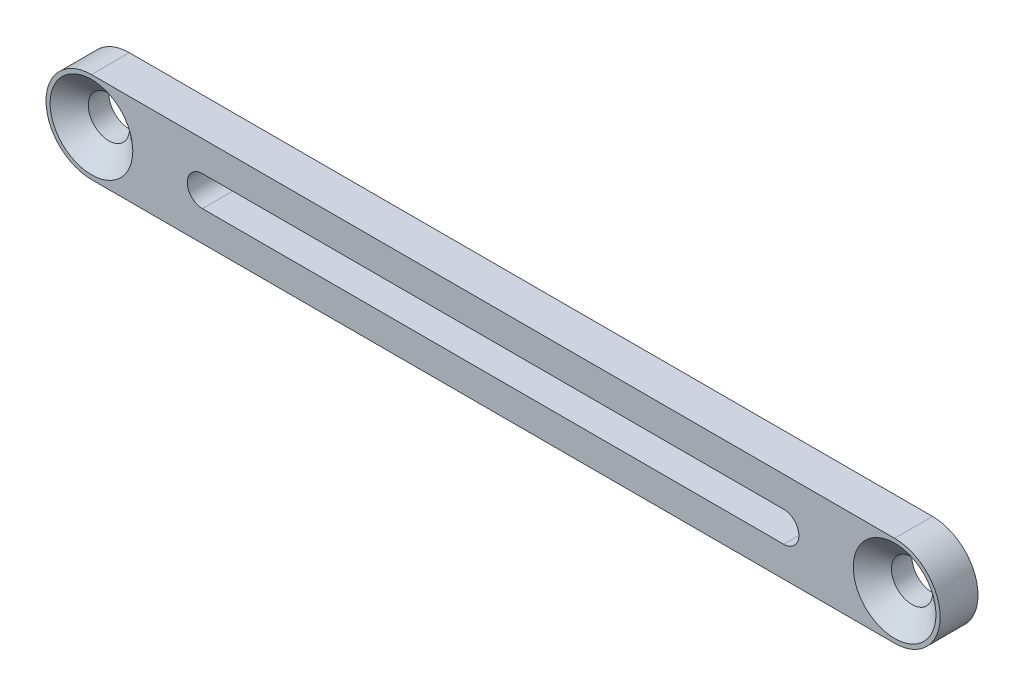
SolidWorks part; units mm, degrees
material "ABS"
ref_plane "Front Plane" through (0, 0, 0) normal (0, 0, 1) x (1, 0, 0)
ref_plane "Top Plane" through (0, 0, 0) normal (0, 1, 0) x (1, 0, 0)
ref_plane "Right Plane" through (0, 0, 0) normal (1, 0, 0) x (0, 0, -1)
sketch "Sketch1" plane through (0, 0, 0) normal (0, 0, 1) x (1, 0, 0)
  line L0 (5.4696, 20.4127) -> (72.7692, 20.4127) construction
  line L1 (5.4696, 16.6027) -> (72.7692, 16.6027)
  line L2 (5.4696, 24.2227) -> (72.7692, 24.2227)
  arc A0 (5.4696, 16.6027) -> (5.4696, 24.2227) centre (5.4696, 20.4127) cw
  arc A1 (72.7692, 16.6027) -> (72.7692, 24.2227) centre (72.7692, 20.4127) ccw
  dimension "D1" = 3.81
  dimension "D2" = 3.81
extrude "Boss-Extrude1" add sketch "Sketch1" along normal blind 3.175
hole_wizard "CSK for #4 Flat Head Machine Screw (100)1" positions "Sketch3" profile "Sketch2" countersink size "#4" standard "ANSI Inch" end condition through all
sketch "Sketch3" plane through (0, 0, 3.175) normal (0, 0, 1) x (1, 0, 0)
  point P0 (5.4696, 20.4127)
  point P3 (72.7692, 20.4127)
sketch "Sketch2" plane through (5.4696, 20.4127, 3.175) normal (1, 0, 0) x (0, -1, 0)
  line L0 (0, 0) -> (0, 3.175)
  line L1 (0, 3.175) -> (1.7272, 3.175)
  line L2 (1.7272, 3.175) -> (1.7272, 1.4564)
  line L3 (1.7272, 1.4564) -> (3.4629, 0)
  line L5 (3.4629, 0) -> (0, 0)
  line L6 (-1.7272, 1.4564) -> (-3.4629, 0) construction
  line L11 (0, -6.35) -> (0, 107.95) construction
  dimension "Thru Hole Dia." = 3.4544
  dimension "Thru Hole Depth" = 3.175
  dimension "Near C'Sink Dia." = 6.9258
  dimension "Near C'Sink Angle" = 100
sketch "Sketch4" plane through (0, 0, 0) normal (0, 0, -1) x (-1, 0, 0)
  line L0 (-72.7692, 20.4127) -> (-5.4696, 20.4127) construction
  line L1 (-63.4728, 20.4127) -> (-14.766, 20.4127) construction
  line L2 (-63.4728, 21.6827) -> (-14.766, 21.6827)
  line L3 (-63.4728, 19.1427) -> (-14.766, 19.1427)
  line L4 (-5.4696, 16.6027) -> (-72.7692, 16.6027) construction
  arc A0 (-63.4728, 21.6827) -> (-63.4728, 19.1427) centre (-63.4728, 20.4127) ccw
  arc A1 (-14.766, 19.1427) -> (-14.766, 21.6827) centre (-14.766, 20.4127) ccw
  point P6 (-39.1194, 20.4127)
  dimension "D1" = 2.54
  dimension "D2" = 9.2964
extrude "Cut-Extrude1" cut sketch "Sketch4" against normal through all
